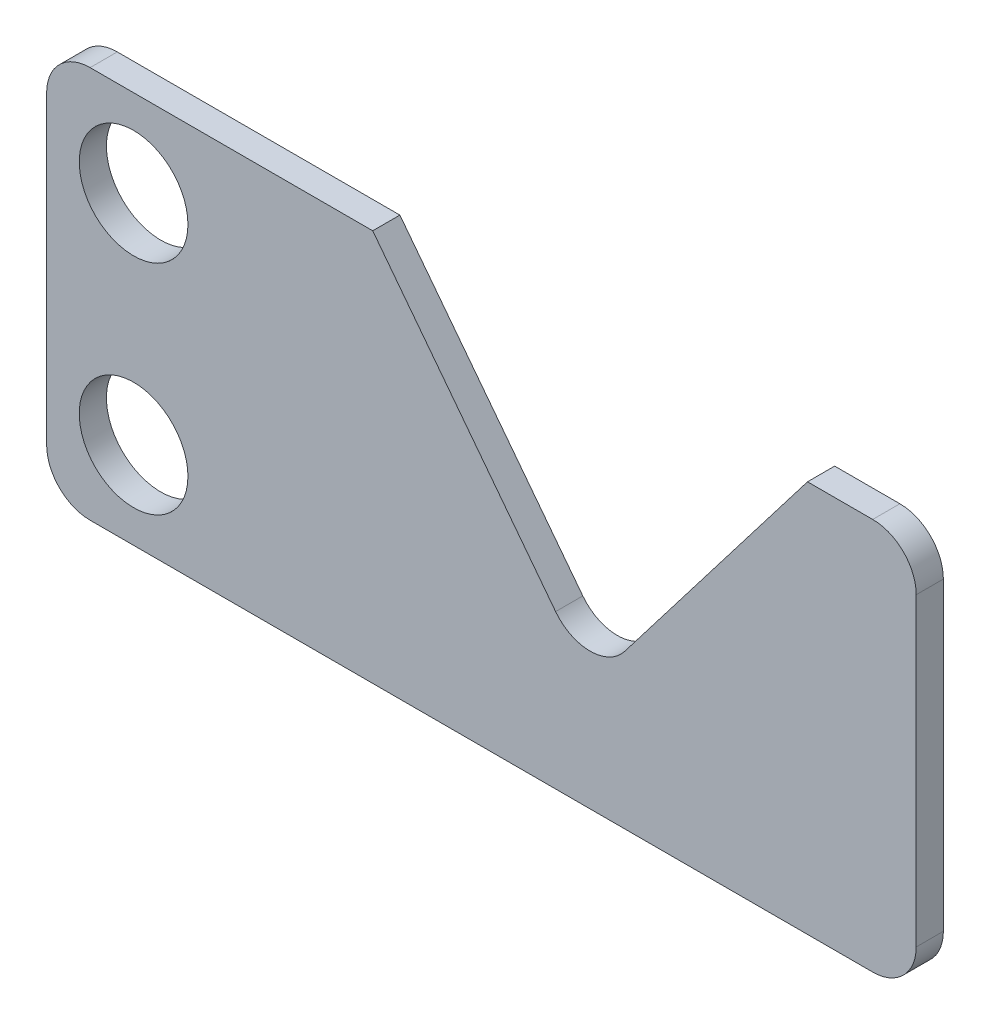
SolidWorks part; units mm, degrees
ref_plane "Front Plane" through (0, 0, 0) normal (0, 0, 1) x (1, 0, 0)
ref_plane "Top Plane" through (0, 0, 0) normal (0, 1, 0) x (1, 0, 0)
ref_plane "Right Plane" through (0, 0, 0) normal (1, 0, 0) x (0, 0, -1)
sketch "Sketch2" plane through (0, 0, 0) normal (0, 0, 1) x (1, 0, 0)
  line L0 (19.05, 22.901) -> (29.7349, 8.9762)
  line L1 (2.54, 0) -> (48.26, 0)
  line L2 (0, 2.54) -> (0, 20.361)
  line L3 (2.54, 22.901) -> (19.05, 22.901)
  line L4 (50.8, 2.54) -> (50.8, 20.361)
  line L5 (33.7651, 8.9762) -> (44.45, 22.901)
  line L6 (44.45, 22.901) -> (48.26, 22.901)
  circle A1 centre (5.08, 17.821) radius 3.175
  circle A2 centre (5.08, 5.08) radius 3.175
  arc A3 (2.54, 0) -> (0, 2.54) centre (2.54, 2.54) cw
  arc A4 (0, 20.361) -> (2.54, 22.901) centre (2.54, 20.361) cw
  arc A5 (29.7349, 8.9762) -> (33.7651, 8.9762) centre (31.75, 10.5224) ccw
  arc A6 (48.26, 22.901) -> (50.8, 20.361) centre (48.26, 20.361) cw
  arc A7 (48.26, 0) -> (50.8, 2.54) centre (48.26, 2.54) ccw
  point P18 (0, 0)
  point P23 (31.75, 6.35)
  point P26 (50.8, 22.901)
  point P29 (50.8, 0)
  dimension "D6" = 5.08
  dimension "D9" = 6.35
  dimension "D10" = 6.35
  dimension "D11" = 2.54
  dimension "D1" = 50.8
  dimension "D2" = 6.35
  dimension "D3" = 25.4
  dimension "D4" = 6.35
  dimension "D5" = 75
  dimension "D7" = 5.08
  dimension "D8" = 5.08
extrude "Boss-Extrude1" add sketch "Sketch2" along normal blind 1.5875
